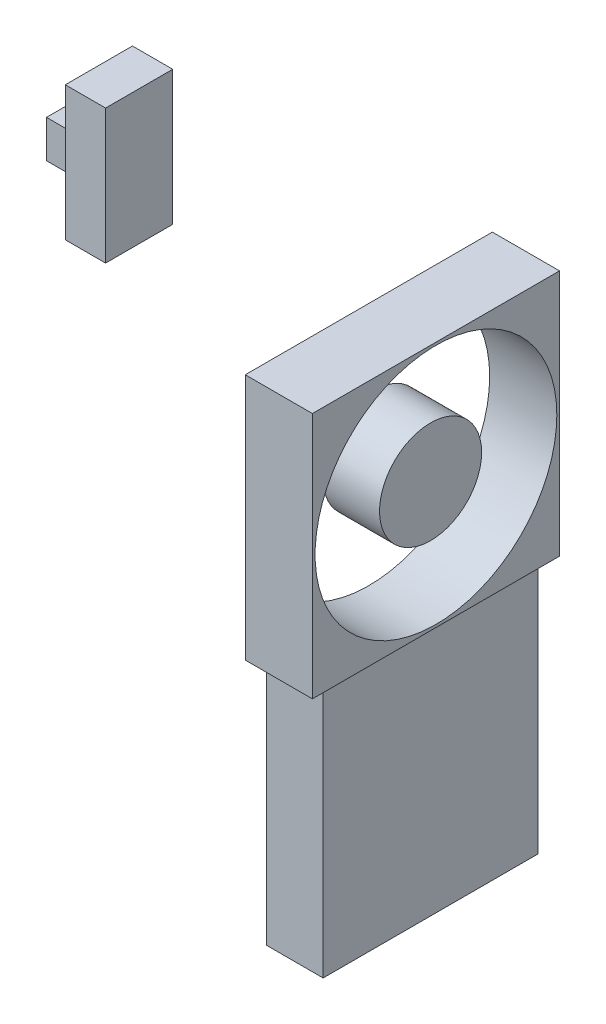
SolidWorks part; units mm, degrees
ref_plane "Front Plane" through (0, 0, 0) normal (0, 0, 1) x (1, 0, 0)
ref_plane "Top Plane" through (0, 0, 0) normal (0, 1, 0) x (1, 0, 0)
ref_plane "Right Plane" through (0, 0, 0) normal (1, 0, 0) x (0, 0, -1)
other "Configuration Table"
sketch "Sketch1" plane through (0, 0, 0) normal (1, 0, 0) x (0, 0, -1)
  line L1 (46, 94) -> (-46, 94)
  line L2 (46, 94) -> (46, 186)
  line L3 (46, 186) -> (-46, 186)
  line L4 (-46, 94) -> (-46, 186)
  line L5 (46, 94) -> (-46, 186) construction
  line L6 (46, 186) -> (-46, 94) construction
extrude "frame" add sketch "Sketch1" along normal blind 25 from offset 158 separate body
sketch "Sketch2" plane through (0, 0, 0) normal (1, 0, 0) x (0, 0, -1)
  circle A0 centre (0, 140) radius 45
extrude "bore" add sketch "Sketch2" along normal blind 27 from offset 157 separate body
combine bodies "Combine1" operation type subtract main body 102 bodies to subtract 103
sketch "Sketch3" plane through (0, 0, 0) normal (1, 0, 0) x (0, 0, -1)
  circle A0 centre (0, 140) radius 19
extrude "hub" add sketch "Sketch3" along normal blind 21 from offset 160 separate body
sketch "Sketch4" plane through (0, 0, 0) normal (1, 0, 0) x (0, 0, -1)
  line L0 (-46, 94) -> (46, 94) construction
  line L1 (40, 0) -> (-40, 0)
  line L2 (40, 0) -> (40, 94)
  line L3 (40, 94) -> (-40, 94)
  line L4 (-40, 0) -> (-40, 94)
  line L5 (40, 0) -> (-40, 94) construction
  line L6 (40, 94) -> (-40, 0) construction
  point P0 (0, 47)
extrude "fan_stand" add sketch "Sketch4" along normal blind 21 from offset 160 separate body
sketch "Sketch5" plane through (0, 0, 0) normal (1, 0, 0) x (0, 0, -1)
  line L1 (-25, 200) -> (-50, 200)
  line L2 (-25, 200) -> (-25, 250)
  line L3 (-25, 250) -> (-50, 250)
  line L4 (-50, 200) -> (-50, 250)
  line L5 (-25, 200) -> (-50, 250) construction
  line L6 (-25, 250) -> (-50, 200) construction
extrude "blower_50mm" add sketch "Sketch5" along normal blind 15 from offset 95 separate body
sketch "Sketch6" plane through (0, 0, 0) normal (1, 0, 0) x (0, 0, -1)
  line L1 (-31, 214) -> (-42, 214)
  line L2 (-31, 214) -> (-31, 228)
  line L3 (-31, 228) -> (-42, 228)
  line L4 (-42, 214) -> (-42, 228)
  line L5 (-31, 214) -> (-42, 228) construction
  line L6 (-31, 228) -> (-42, 214) construction
extrude "blower_nozzle" add sketch "Sketch6" along normal blind 15 from offset 80 separate body
